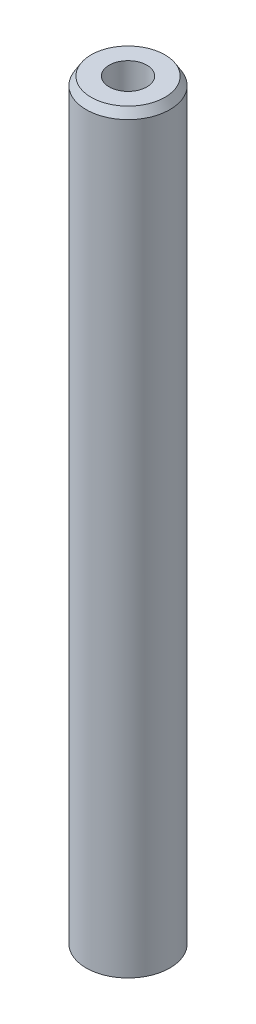
SolidWorks part; units mm, degrees
ref_plane "Front Plane" through (0, 0, 0) normal (0, 0, 1) x (1, 0, 0)
ref_plane "Top Plane" through (0, 0, 0) normal (0, 1, 0) x (1, 0, 0)
ref_plane "Right Plane" through (0, 0, 0) normal (1, 0, 0) x (0, 0, -1)
sketch "Sketch1" plane through (0, 0, 0) normal (0, 1, 0) x (1, 0, 0)
  circle A0 centre (0, 0) radius 20
  dimension "SHAFT_OD" = 40
extrude "Boss-Extrude1" add sketch "Sketch1" along normal blind 361.6315
sketch "Sketch2" plane through (0, 0, 0) normal (0, 1, 0) x (1, 0, 0)
  circle A0 centre (0, 0) radius 9.0148
  dimension "BORE_D" = 18.0296
extrude "Cut-Extrude1" cut sketch "Sketch2" along normal through all
chamfer "Chamfer1" distance 3.9153 angle 31.281 2 edges at (0, 361.6315, 20) (0, 0, 20) first distance on face at (0, 361.6315, 20) first distance on face at (0, 0, 9.0148)
